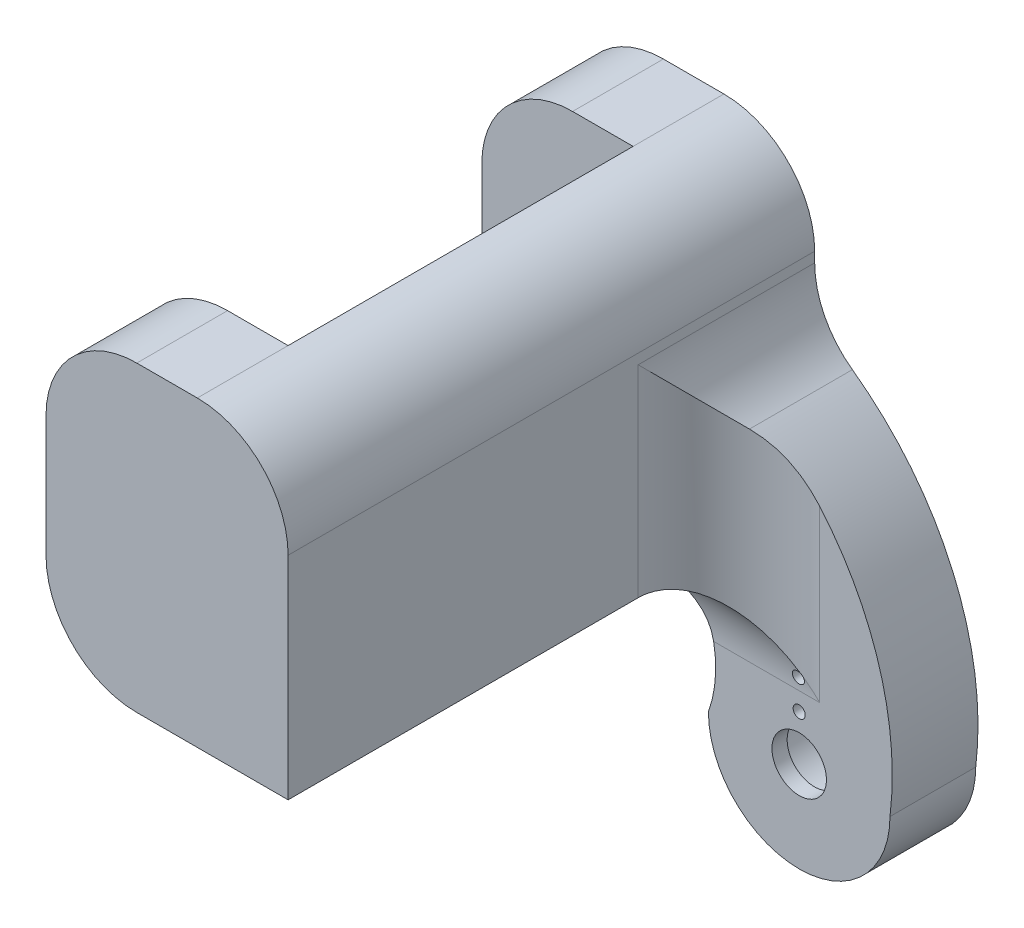
SolidWorks part; units mm, degrees
other "Marca1"
sketch "Croquis5" plane through (-41.9891, 32, -45) normal (-0.9335, 0.1055, -0.3427) x (-0.3417, 0.0277, 0.9394)
ref_plane "Alzado" through (0, 0, 0) normal (0, 0, 1) x (1, 0, 0)
ref_plane "Planta" through (0, 0, 0) normal (0, 1, 0) x (1, 0, 0)
ref_plane "Vista lateral" through (0, 0, 0) normal (1, 0, 0) x (0, 0, -1)
sketch "Croquis1" plane through (0, 0, 0) normal (1, 0, 0) x (0, 0, -1)
  line L0 (0, 42) -> (0, -48) construction
  line L2 (-42, 32) -> (-27, 32)
  line L3 (-42, 32) -> (-42, -18)
  line L4 (-42, -18) -> (-27, -18)
  line L5 (-27, 32) -> (-27, -18)
  line L6 (30, 32) -> (45, 32)
  line L7 (30, 32) -> (30, -18)
  line L8 (30, -18) -> (45, -18)
  line L9 (45, 32) -> (45, -18)
  dimension "D1" = 15
  dimension "D2" = 15
  dimension "D3" = 57
  dimension "D4" = 30
  dimension "D5" = 50
  dimension "D6" = 10
extrude "Saliente-Extruir1" add sketch "Croquis1" along normal blind 25
sketch "Croquis2" plane through (25, 0, 0) normal (-1, 0, 0) x (0, 0, 1)
  line L1 (-45, 32) -> (42, 32)
  line L2 (-45, 32) -> (-45, -18)
  line L3 (-45, -18) -> (42, -18)
  line L4 (42, 32) -> (42, -18)
extrude "Saliente-Extruir2" add sketch "Croquis2" against normal blind 15
sketch "Croquis6" plane through (0, 0, -45) normal (0, 0, -1) x (-1, 0, 0)
  line L0 (-40, 7) -> (-40, -18)
  line L1 (-40, 32) -> (-40, -18) construction
  line L2 (-40, -18) -> (-25, -18)
  line L3 (-40, -18) -> (0, -18) construction
  arc A0 (-66.61, -43.5) -> (-36.61, -43.5) centre (-51.61, -43.5) ccw
  arc A1 (-66.61, -43.5) -> (-40, 7) centre (-16.985, -37.3881) cw
  arc A2 (-36.61, -43.5) -> (-25, -18) centre (-17.8143, -36.6646) cw
  dimension "D1" = 30
  dimension "D6" = 20
  dimension "D7" = 50
  dimension "D2" = 25
  dimension "D3" = 25
  dimension "D4" = 25.5
  dimension "D5" = 26.61
extrude "Saliente-Extruir3" add sketch "Croquis6" against normal blind 14.17
fillet "Redondeo1" radius 15 3 edges at (32.5, -18, -30.83) (40, -5.5, -30.83) (40, 7, -37.915)
sketch "Croquis7" plane through (0, 0, -45) normal (0, 0, -1) x (-1, 0, 0)
  arc A4 (-57.6731, -39.0854) -> (-45.5469, -39.0854) centre (-51.61, -43.5) ccw
  arc A5 (-48.61, -25.5) -> (-54.61, -25.5) centre (-51.61, -25.5) ccw
  arc A6 (-57.6731, -39.0854) -> (-54.61, -25.5) centre (-153.4559, -10.351) ccw
  arc A7 (-45.5469, -39.0854) -> (-48.61, -25.5) centre (50.2359, -10.351) cw
  arc A8 (-66.61, -43.5) -> (-36.61, -43.5) centre (-51.61, -43.5) ccw construction
  dimension "D8" = 15
  dimension "D9" = 6
  dimension "D10" = 18
  dimension "D11" = 100
  dimension "D12" = 100
extrude "Cortar-Extruir1" cut sketch "Croquis7" against normal blind 11.66
sketch "Croquis8" plane through (0, 0, -33.34) normal (0, 0, -1) x (-1, 0, 0)
  circle A0 centre (-51.61, -43.5) radius 4.5
  circle A1 centre (-51.61, -36) radius 1
  circle A2 centre (-51.61, -31) radius 1
  dimension "D1" = 9
  dimension "D2" = 2
  dimension "D3" = 2
  dimension "D4" = 7.5
  dimension "D5" = 5
extrude "Cortar-Extruir2" cut sketch "Croquis8" against normal through all
fillet "Redondeo2" radius 15 4 edges at (0, 32, 34.5) (0, -18, -37.5) (0, -18, 34.5) (0, 32, -37.5)
fillet "Redondeo3" radius 15 1 edges at (40, 32, -1.5)
